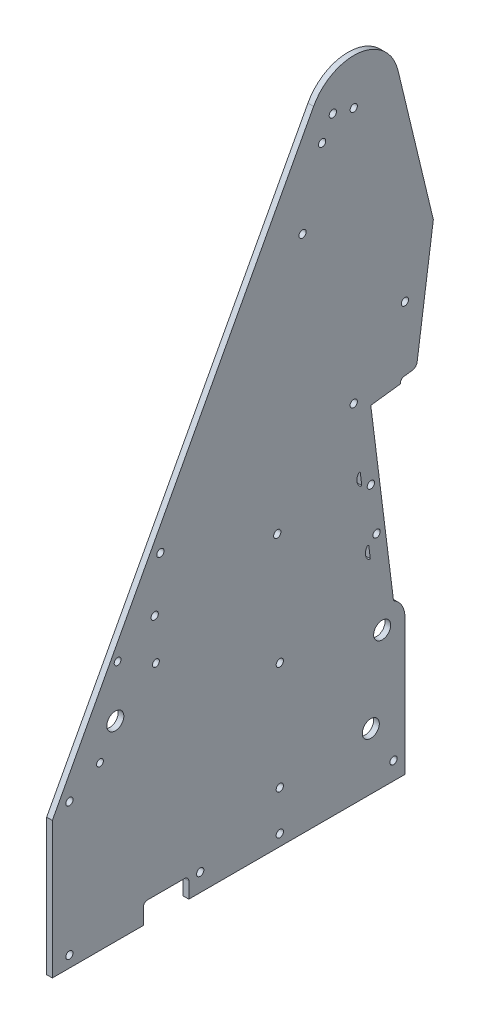
SolidWorks part; units mm, degrees
ref_plane "Front Plane" through (0, 0, 0) normal (0, 0, 1) x (1, 0, 0)
ref_plane "Top Plane" through (0, 0, 0) normal (0, 1, 0) x (1, 0, 0)
ref_plane "Right Plane" through (0, 0, 0) normal (1, 0, 0) x (0, 0, -1)
sketch "Sketch1" plane through (0, 0, 0) normal (1, 0, 0) x (0, 0, -1)
  line L0 (0, 0) -> (0, 76.2)
  line L6 (-19.05, 188.0016) -> (-2.512, 190.0852)
  line L7 (6.4943, 193.62) -> (15.875, 260.35)
  line L8 (15.875, 260.35) -> (-3.8791, 342.4892)
  line L9 (-50.965, 348.5436) -> (-196.85, 76.2)
  line L10 (-196.85, 0) -> (0, 0)
  line L11 (-196.85, 76.2) -> (-196.85, 0)
  line L12 (-19.05, 188.0016) -> (-6.35, 87.1985)
  line L13 (-0.4471, 192.7455) -> (6.4943, 193.62)
  line L14 (-2.512, 190.0852) -> (-3.1086, 194.8203) construction
  line L15 (-2.512, 190.0852) -> (6.1508, 191.1766) construction
  line L16 (6.1508, 191.1766) -> (6.4943, 193.62) construction
  arc A0 (-3.8791, 342.4892) -> (-50.965, 348.5436) centre (-28.575, 336.55) ccw
  arc A3 (0, 76.2) -> (-6.35, 87.1985) centre (-12.7, 76.2) ccw
  arc A4 (-2.512, 190.0852) -> (-0.4471, 192.7455) centre (-0.1494, 190.3829) cw
  dimension "D2" = 25.4
  dimension "D6" = 196.85
  dimension "D7" = 76.2
  dimension "D12" = 12.7
  dimension "D8" = 19.05
  dimension "D10" = 2.3813
  dimension "D1" = 28.575
  dimension "D3" = 336.55
  dimension "D4" = 25.4
  dimension "D5" = 101.6
  dimension "D9" = 6.35
  dimension ".5" = 12.7
  dimension "D11" = 76.2
  dimension "D13" = 76.2
  dimension "D14" = 15.875
  dimension "D15" = 6.35
extrude "Boss-Extrude1" add sketch "Sketch1" along normal blind 3.175
sketch "Sketch2" plane through (3.175, 0, 0) normal (1, 0, 0) x (0, 0, -1)
  line L16 (-146.05, 8.7909) -> (-146.05, -0.3034) construction
  line L17 (-123.0376, 11.1785) -> (-143.6624, 11.1785) construction
  line L18 (-120.65, -0.3034) -> (-120.65, 8.7909) construction
  line L19 (-146.05, 8.7909) -> (-146.05, 0)
  line L20 (-123.0376, 11.1785) -> (-143.6624, 11.1785)
  line L21 (-120.65, 0) -> (-120.65, 8.7909)
  line L25 (-146.05, 0) -> (-120.65, 0)
  line L26 (-196.85, 0) -> (0, 0) construction
  line L33 (-223.2996, 0) -> (-223.2996, 6.35) construction
  line L34 (-229.6496, 0) -> (-223.2996, 0) construction
  line L35 (-229.6496, 6.35) -> (-229.6496, 0) construction
  line L36 (-223.2996, 6.35) -> (-229.6496, 6.35) construction
  line L37 (-223.2996, 0) -> (-223.2996, 6.35)
  line L38 (-229.6496, 0) -> (-223.2996, 0)
  line L39 (-229.6496, 6.35) -> (-229.6496, 0)
  line L40 (-223.2996, 6.35) -> (-229.6496, 6.35)
  arc A0 (-143.6624, 11.1785) -> (-146.05, 8.7909) centre (-143.6624, 8.7909) ccw construction
  arc A1 (-120.65, 8.7909) -> (-123.0376, 11.1785) centre (-123.0376, 8.7909) ccw construction
  arc A2 (-143.6624, 11.1785) -> (-146.05, 8.7909) centre (-143.6624, 8.7909) ccw
  arc A3 (-120.65, 8.7909) -> (-123.0376, 11.1785) centre (-123.0376, 8.7909) ccw
extrude "Cut-Extrude1" cut sketch "Sketch2" against normal through all
sketch "Sketch3" plane through (3.175, 0, 0) normal (1, 0, 0) x (0, 0, -1)
  point P4 (-12.7, 76.2)
hole_wizard "3/8 Clearance Hole1" positions "Sketch3" profile "Sketch4" hole size "3/8" standard "ANSI Inch" end condition up to next
sketch "Sketch4" plane through (3.175, 76.2, 12.7) normal (0, 1, 0) x (0, 0, -1)
  line L0 (0, 0) -> (0, 3.175)
  line L1 (0, 3.175) -> (4.7625, 3.175)
  line L2 (4.7625, 3.175) -> (4.7625, 0)
  line L5 (4.7625, 0) -> (0, 0)
  line L11 (0, -6.35) -> (0, 107.95) construction
  dimension "Thru Hole Dia." = 9.525
  dimension "Thru Hole Depth" = 3.175
sketch "Sketch5" plane through (3.175, 0, 0) normal (1, 0, 0) x (0, 0, -1)
  line L0 (-12.7, 76.2) -> (19.6681, 37.0472)
  line L1 (19.6681, 37.0472) -> (18.4836, 24.56)
  line L2 (15.6221, 41.9413) -> (-25.2806, 17.5464)
  line L3 (-15.875, 19.05) -> (-25.2806, 17.5464)
  line L4 (0, 0) -> (0, 76.2) construction
  line L5 (-15.875, 19.05) -> (-27.0501, 3.6221)
  line L6 (-27.0501, 3.6221) -> (-54.7505, 169.5016)
  line L7 (50.8, 0) -> (50.8, 73.5762) construction
  dimension "D1" = 44.45
  dimension "D2" = 50.8
  dimension "D3" = 45
  dimension "D4" = 60.325
  dimension "D5" = 19.05
  dimension "D6" = 15.875
  dimension "D7" = 9.525
  dimension "D8" = 47.625
  dimension "D9" = 19.05
  dimension "D10" = 45
  dimension "D11" = 50.8
sketch "Sketch6" plane through (3.175, 0, 0) normal (1, 0, 0) x (0, 0, -1)
  circle A3 centre (-161.7015, 106.7172) radius 4.7625
  circle A5 centre (-161.7015, 106.7172) radius 6.985 construction
  circle A8 centre (-160.3992, 134.8341) radius 1.905 construction
  circle A9 centre (-139.0167, 123.3803) radius 1.905 construction
  arc A10 (-168.5468, 89.9048) -> (-169.3474, 92.4435) centre (-170.2469, 90.7642) ccw construction
  arc A11 (-169.3474, 92.4435) -> (-171.9044, 91.7033) centre (-170.2469, 90.7642) ccw construction
  arc A12 (-171.9044, 91.7033) -> (-168.5468, 89.9048) centre (-170.2469, 90.7642) ccw construction
  circle A17 centre (-160.3992, 134.8341) radius 1.905
  circle A18 centre (-139.0167, 123.3803) radius 1.905
  arc A19 (-168.5468, 89.9048) -> (-169.3474, 92.4435) centre (-170.2469, 90.7642) ccw
  arc A20 (-169.3474, 92.4435) -> (-171.9044, 91.7033) centre (-170.2469, 90.7642) ccw
  arc A21 (-171.9044, 91.7033) -> (-168.5468, 89.9048) centre (-170.2469, 90.7642) ccw
  dimension "D1" = 9.525
extrude "Cut-Extrude2" cut sketch "Sketch6" against normal through all
sketch "Sketch10" plane through (3.175, 0, 0) normal (1, 0, 0) x (0, 0, -1)
  circle A0 centre (-71.2566, 151.9429) radius 2.032
  dimension "D1" = 4.064
extrude "Cut-Extrude4" cut sketch "Sketch10" against normal through all
sketch "Sketch11" plane through (3.175, 0, 0) normal (1, 0, 0) x (0, 0, -1)
  circle A0 centre (-187.325, 80.5336) radius 2.032
  circle A1 centre (-187.325, 6.35) radius 2.032
  circle A2 centre (-187.325, 6.35) radius 2.032 construction
  circle A3 centre (-187.325, 80.5336) radius 2.032 construction
  dimension "D1" = 4.064
extrude "Cut-Extrude5" cut sketch "Sketch11" against normal through all
sketch "Sketch13" plane through (0, 0, 0) normal (-1, 0, 0) x (0, 0, 1)
  circle A0 centre (40.2353, 339.6611) radius 2.032
  circle A1 centre (46.232, 328.466) radius 2.032
  circle A2 centre (40.2353, 339.6611) radius 1.905 construction
  circle A3 centre (46.232, 328.466) radius 1.905 construction
  dimension "D1" = 4.064
extrude "Cut-Extrude6" cut sketch "Sketch13" against normal through all
sketch "Sketch14" plane through (3.175, 0, 0) normal (1, 0, 0) x (0, 0, -1)
  line L0 (-50.965, 348.5436) -> (-196.85, 76.2) construction
  line L1 (-136.525, 175.369) -> (-142.1225, 178.3674) construction
  circle A0 centre (-136.525, 175.369) radius 2.032
  dimension "D1" = 4.064
  dimension "D2" = 6.35
  dimension "D3" = 136.525
extrude "Cut-Extrude7" cut sketch "Sketch14" against normal through all
sketch "Sketch15" plane through (3.175, 0, 0) normal (1, 0, 0) x (0, 0, -1)
  circle A0 centre (-19.05, 31.75) radius 4.7625
  circle A1 centre (-12.7, 76.2) radius 4.7625 construction
  circle A2 centre (-28.575, 193.675) radius 2.032
  dimension "D1" = 44.45
  dimension "D3" = 4.064
  dimension "D2" = 6.35
  dimension "D4" = 161.925
  dimension "D5" = 9.525
extrude "Cut-Extrude8" cut sketch "Sketch15" against normal through all
sketch "Sketch16" plane through (3.175, 0, 0) normal (1, 0, 0) x (0, 0, -1)
  line L0 (-24.978, 158.8539) -> (-24.0851, 151.7662)
  line L1 (-6.35, 87.1985) -> (-19.05, 188.0016) construction
  line L2 (-20.2155, 121.0527) -> (-21.0031, 120.9535)
  line L3 (-24.978, 158.8539) -> (-25.7656, 158.7547)
  line L4 (-24.0851, 151.7662) -> (-24.8726, 151.667)
  line L5 (-12.7, 137.6001) -> (-26.6484, 135.8427) construction
  line L6 (-19.3226, 113.965) -> (-20.1101, 113.8658)
  line L7 (-19.3226, 113.965) -> (-20.2155, 121.0527)
  line L8 (-25.3253, 161.6102) -> (-23.7378, 149.0099) construction
  arc A0 (-25.7656, 158.7547) -> (-24.8726, 151.667) centre (-21.7352, 155.6624) ccw
  arc A1 (-20.1101, 113.8658) -> (-21.0031, 120.9535) centre (-16.9727, 117.8612) cw
  circle A2 centre (-19.0126, 149.6052) radius 2.032
  circle A3 centre (-15.8376, 124.4044) radius 2.032
  point P2 (-24.5315, 155.31)
  dimension "D2" = 0.7937
  dimension "D3" = 5.08
  dimension "D5" = 4.064
  dimension "D1" = 7.1437
  dimension "D4" = 38.1
  dimension "D6" = 4.7625
  dimension "D7" = 25.4
extrude "Cut-Extrude9" cut sketch "Sketch16" against normal up to next
fillet "Fillet1" radius 3.175 1 edges at (1.5875, 193.62, -6.4943)
sketch "Sketch17" plane through (3.175, 0, 0) normal (1, 0, 0) x (0, 0, -1)
  circle A0 centre (-6.35, 9.9085) radius 2.032
  circle A1 centre (-69.85, 6.35) radius 2.032
  circle A2 centre (-114.3, 9.9085) radius 2.032
  circle A3 centre (-114.3, 9.9085) radius 1.905 construction
  circle A4 centre (-69.85, 6.35) radius 2.286 construction
  circle A5 centre (-6.35, 9.9085) radius 1.905 construction
  circle A6 centre (-69.85, 28.575) radius 2.032
  circle A7 centre (-69.85, 28.575) radius 1.905 construction
  dimension "D1" = 4.064
extrude "Cut-Extrude10" cut sketch "Sketch17" against normal through all
sketch "Sketch18" plane through (0, 0, 0) normal (-1, 0, 0) x (0, 0, 1)
  line L0 (50.965, 348.5436) -> (196.85, 76.2) construction
  circle A0 centre (0, 228.6) radius 2.032
  circle A1 centre (69.85, 88.9) radius 2.032
  circle A2 centre (139.7, 146.5801) radius 2.032
  circle A3 centre (57.15, 289.9291) radius 2.032
  dimension "D1" = 4.064
  dimension "D2" = 228.6
  dimension "D4" = 17.145
  dimension "D5" = 139.7
  dimension "D6" = 22.225
  dimension "D7" = 57.15
  dimension "D8" = 69.85
  dimension "D9" = 88.9
extrude "Cut-Extrude11" cut sketch "Sketch18" against normal through all
sketch "Sketch19" plane through (0, 0, 0) normal (-1, 0, 0) x (0, 0, 1)
  circle A0 centre (28.575, 336.55) radius 2.032
  arc A1 (50.965, 348.5436) -> (3.8791, 342.4892) centre (28.575, 336.55) ccw construction
  dimension "D1" = 4.064
extrude "Cut-Extrude12" cut sketch "Sketch19" against normal through all
